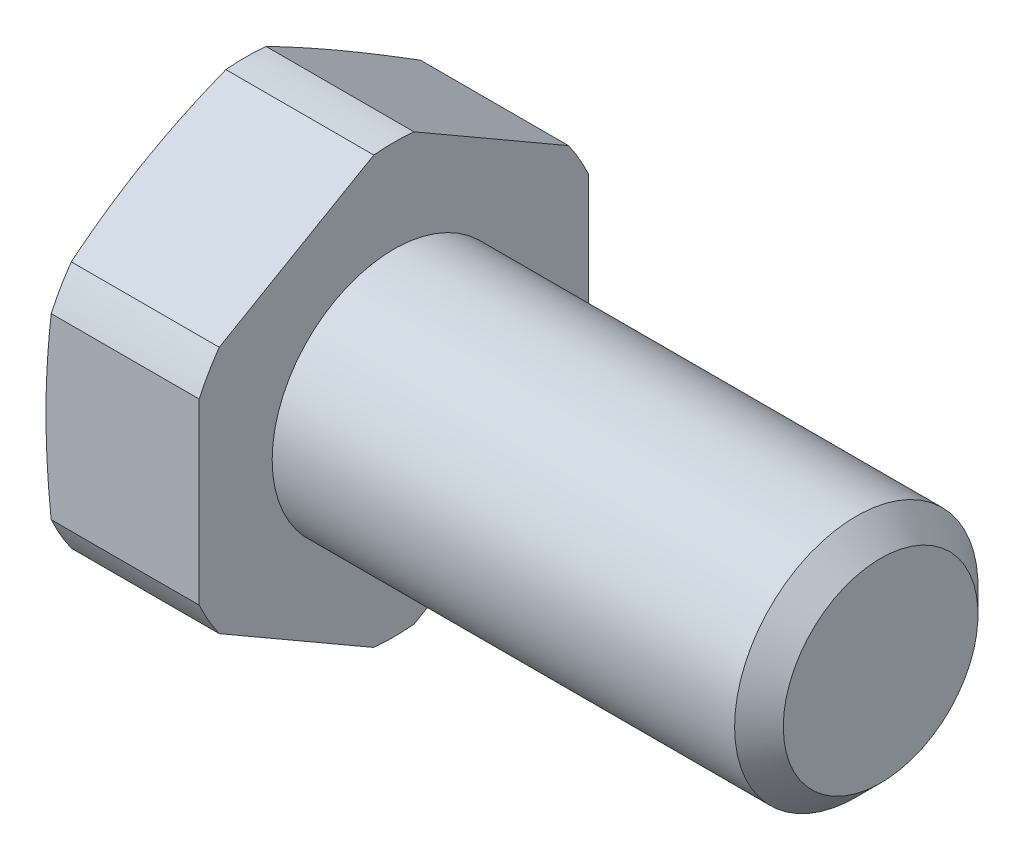
SolidWorks part; units mm, degrees
material "AISI 1020"
ref_plane "Спереди" through (0, 0, 0) normal (0, 0, 1) x (1, 0, 0)
ref_plane "Сверху" through (0, 0, 0) normal (0, 1, 0) x (1, 0, 0)
ref_plane "Справа" through (0, 0, 0) normal (1, 0, 0) x (0, 0, -1)
sketch "Эскиз1" plane through (0, 0, 0) normal (0, 0, 1) x (1, 0, 0)
  line L0 (-1000, 0) -> (49000, 0) construction
  line L1 (-6.4, 0) -> (-6.4, 7.6)
  line L2 (-6.4, 7.6) -> (-6.0785, 8.8)
  line L3 (-6.0785, 8.8) -> (0, 8.8)
  line L4 (0, 8.8) -> (0, 5)
  line L5 (0, 5) -> (19, 5)
  line L6 (20, 4) -> (20, 0)
  line L7 (20, 5) -> (20.75, 6.299) construction
  line L8 (20.75, 6.299) -> (21.5, 5) construction
  line L9 (21.5, 5) -> (20, 5) construction
  line L10 (20.75, 6.299) -> (20.75, 5) construction
  line L11 (20.75, 6.299) -> (0.75, 6.299) construction
  line L12 (19, 5) -> (20, 4)
  line L13 (20, 5) -> (19.5, 4.5) construction
  line L14 (-6.4, 7.6) -> (-22.4, 7.6) construction
  line L15 (-6.4, 0) -> (20, 0)
  dimension "D1" = 1
  dimension "D2" = 15
revolve "Повернуть1" add sketch "Эскиз1" angle 360 about L0
cosmetic thread "Условное изображение резьбы1" parameters "D1"=20, "D2"=7.4019
sketch "Эскиз2" plane through (-6.4, 0, 0) normal (-1, 0, 0) x (0, 0, 1)
  line L1 (0, 9.2376) -> (-8, 4.6188)
  line L2 (-8, 4.6188) -> (-8, -4.6188)
  line L3 (-8, -4.6188) -> (0, -9.2376)
  line L4 (0, -9.2376) -> (8, -4.6188)
  line L5 (8, -4.6188) -> (8, 4.6188)
  line L6 (8, 4.6188) -> (0, 9.2376)
  circle A0 centre (0, 0) radius 8 construction
  dimension "D1" = 16
extrude "Вырез-Вытянуть1" cut sketch "Эскиз2" against normal up to surface (26.4 mm away) flip side to cut up to face at (20, 0, 4)
equation "\"D1@Эскиз1\"=\"_d_@Эскиз1\"/10"
equation "\"D@Эскиз1\"=\"S_@Эскиз1\"*0.95"
equation "\"D1@Эскиз2\"=\"S_@Эскиз1\""
equation "\"D1@Условное изображение резьбы1\"=\"b_@Эскиз1\""
equation "\"D2@Условное изображение резьбы1\"=\"_d_@Эскиз1\"-\"dr@Эскиз1\"*2"
